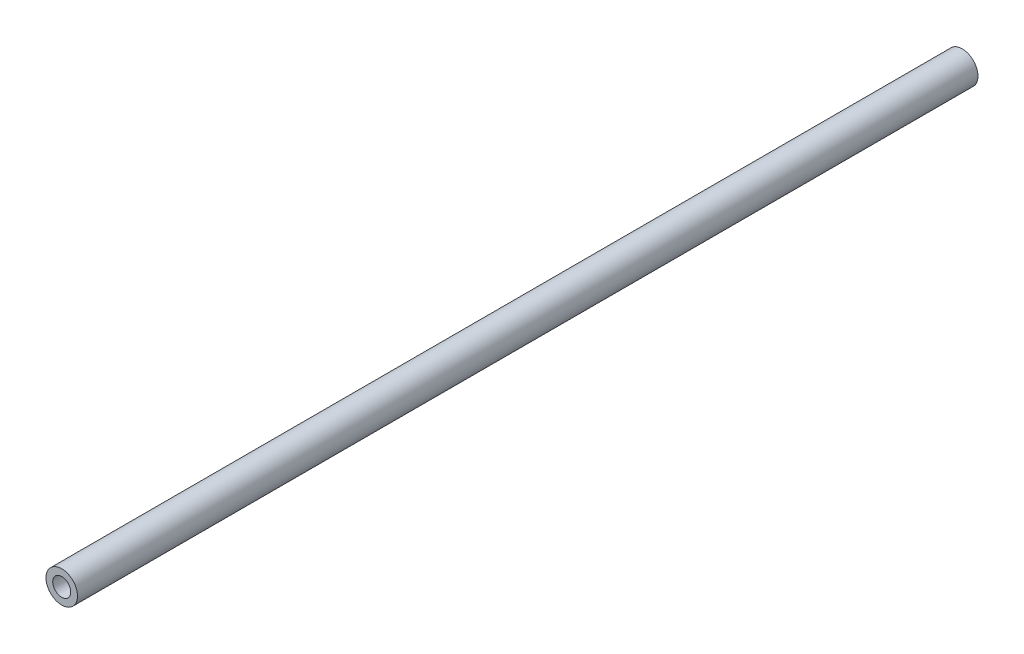
SolidWorks part; units mm, degrees
ref_plane "Front Plane" through (0, 0, 0) normal (0, 0, 1) x (1, 0, 0)
ref_plane "Top Plane" through (0, 0, 0) normal (0, 1, 0) x (1, 0, 0)
ref_plane "Right Plane" through (0, 0, 0) normal (1, 0, 0) x (0, 0, -1)
sketch "Sketch1" plane through (0, 0, 0) normal (0, 0, 1) x (1, 0, 0)
  circle A0 centre (0, 0) radius 3.5
  dimension "D1" = 7
extrude "Boss-Extrude1" add sketch "Sketch1" along normal blind 200
sketch "Sketch2" plane through (0, 0, 0) normal (0, 0, -1) x (-1, 0, 0)
  circle A0 centre (0, 0) radius 2
  dimension "D1" = 4
extrude "Cut-Extrude1" cut sketch "Sketch2" against normal blind 15
sketch "Sketch4" plane through (0, 0, 200) normal (0, 0, 1) x (1, 0, 0)
  circle A0 centre (0, 0) radius 2
  dimension "D1" = 4
extrude "Cut-Extrude3" cut sketch "Sketch4" against normal blind 20
